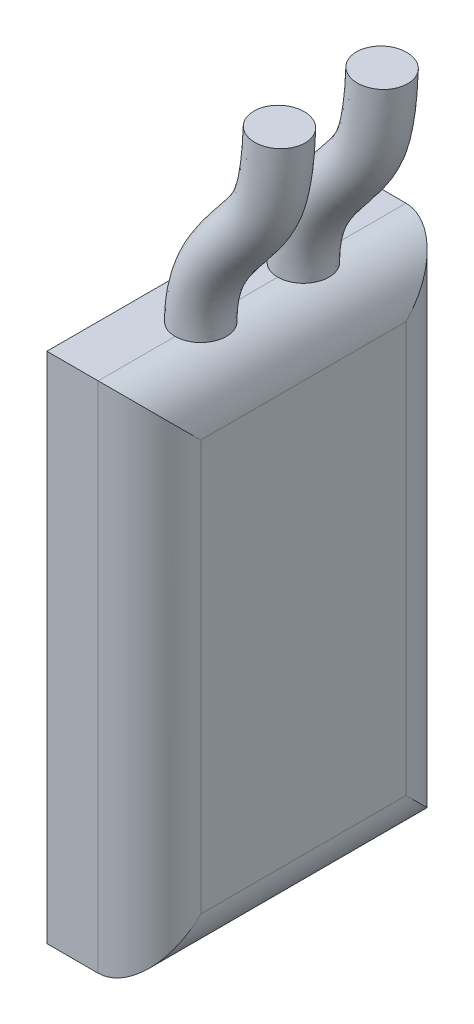
SolidWorks part; units mm, degrees
ref_plane "Front Plane" through (0, 0, 0) normal (0, 0, 1) x (1, 0, 0)
ref_plane "Top Plane" through (0, 0, 0) normal (0, 1, 0) x (1, 0, 0)
ref_plane "Right Plane" through (0, 0, 0) normal (1, 0, 0) x (0, 0, -1)
sketch "Sketch5" plane through (0, 0, 0) normal (0, 1, 0) x (1, 0, 0)
  line L0 (0.9842, 2.889) -> (0.9842, -0.111) construction
  line L1 (1.4842, 2.889) -> (0.4842, 2.889)
  line L2 (1.4842, 2.889) -> (1.4842, -0.111)
  line L3 (1.4842, -0.111) -> (0.4842, -0.111)
  line L4 (0.4842, 2.889) -> (0.4842, -0.111)
  point P4 (0.9842, 1.389)
  point P7 (0.9842, 0.889)
  point P8 (0.9842, 1.889)
  dimension "D1" = 1
  dimension "D2" = 3
  dimension "D3" = 0.5
  dimension "D4" = 0.5
extrude "Boss-Extrude3" add sketch "Sketch5" against normal blind 5 separate body
ref_plane "Plane3" through (0, 0, -0.889) normal (0, 0, 1) x (1, 0, 0)
sketch "Sketch3" plane through (0, 0, 0) normal (0, 1, 0) x (1, 0, 0)
  circle A1 centre (0.9842, 1.889) radius 0.25
  circle A2 centre (0.9842, 0.889) radius 0.25
  point P0 (0.9842, 0.889)
  point P1 (0.9842, 1.889)
  point P2 (1.0456, 1.8668)
  point P3 (1.1003, 0.6558)
  point P4 (0.9842, 1.889)
  point P9 (8.4195, 3.5824)
  point P10 (0.9842, 0.889)
  dimension "D3" = 0.5
sketch "Sketch4" plane through (2.3105, 0, -0.889) normal (0, 0, -1) x (-1, 0, 0)
  spline S0 degree 3 poles (1.3263, 0) (1.3263, 0.5421) (0.8588, 0.9275) (0.5808, 1.4576) (0.5592, 2.0264) knots 0 0 0 0 0.649588 1 1 1 1
  point P7 (1.8116, 1.6586)
  point P9 (0.5592, 2.0264)
  point P10 (0.7989, 1.1039)
  point P11 (0, 0)
fillet "Fillet1" radius 0.5 4 edges at (1.4842, -2.5, -2.889) (1.4842, -5, -1.389) (1.4842, -2.5, 0.111) (1.4842, 0, -1.389)
sweep "Sweep1" add profiles "Sketch3" path "Sketch4"
